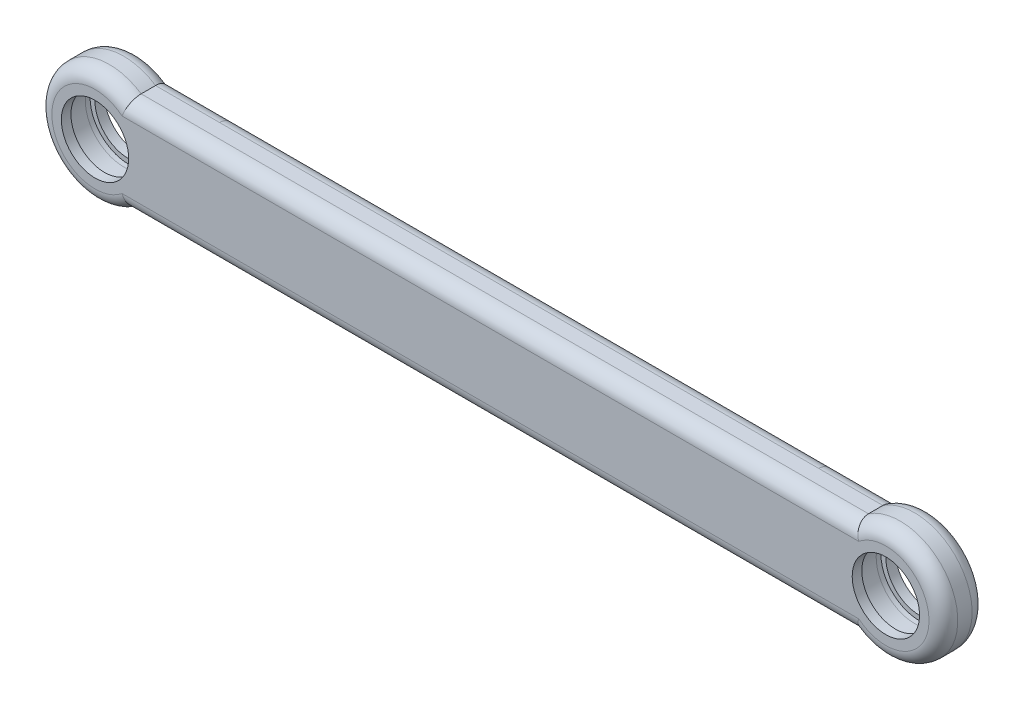
SolidWorks part; units mm, degrees
ref_plane "Front Plane" through (0, 0, 0) normal (0, 0, 1) x (1, 0, 0)
ref_plane "Top Plane" through (0, 0, 0) normal (0, 1, 0) x (1, 0, 0)
ref_plane "Right Plane" through (0, 0, 0) normal (1, 0, 0) x (0, 0, -1)
sketch "Sketch6" plane through (0, 0, 0) normal (0, 0, 1) x (1, 0, 0)
  line L0 (6.6332, -10) -> (158.3668, -10)
  line L2 (6.6332, 10) -> (158.3668, 10)
  line L3 (-58.5211, 0) -> (213.089, 0) construction
  line L6 (82.5, 22.0784) -> (82.5, -23.3181) construction
  line L13 (20, 10) -> (20, -10)
  line L14 (145, 10) -> (145, -10)
  circle A2 centre (165, 0) radius 12 construction
  circle A3 centre (0, 0) radius 8.025
  circle A4 centre (0, 0) radius 12 construction
  circle A8 centre (0, 0) radius 7.025
  circle A12 centre (13, 0) radius 2.2
  arc A14 (6.6332, 10) -> (6.6332, -10) centre (0, 0) ccw
  circle A15 centre (152, 0) radius 2.2
  circle A16 centre (165, 0) radius 7.025
  circle A17 centre (165, 0) radius 8.025
  arc A18 (158.3668, 10) -> (158.3668, -10) centre (165, 0) cw
  dimension "D2" = 1
  dimension "D3" = 165
  dimension "D4" = 16.05
  dimension "D5" = 24
  dimension "D6" = 1
  dimension "D7" = 7
  dimension "D8" = 20
  dimension "D10" = 4.4
extrude "Boss-Extrude1" add sketch "Sketch6" along normal blind 9 contours L2 A18 L0 A14
extrude "Cut-Extrude1" cut sketch "Sketch6<23>" along normal offset from surface (5 mm away) 2 from offset 2 contours A3 | A17 up to face at (82.5, 0, 9)
sketch "Sketch6<23>" plane through (0, 0, 0) normal (0, 0, 1) x (1, 0, 0) same geometry as "Sketch6"
extrude "Cut-Extrude2" cut sketch "Sketch6<24>" along normal through all contours A8 | A16
sketch "Sketch6<24>" plane through (0, 0, 0) normal (0, 0, 1) x (1, 0, 0) same geometry as "Sketch6"
fillet "Fillet1" radius 3 8 edges at (-12, 0, 9) (177, 0, 9) (82.5, -10, 9) (82.5, 10, 9) (82.5, -10, 0) (82.5, 10, 0) (177, 0, 0) (-12, 0, 0)
hole_wizard "CSK for M3 Flat Head Machine Screw1" positions "Sketch7" profile "Sketch8" countersink size "M3" standard "ANSI Metric"
sketch "Sketch7" plane through (0, 0, 0) normal (0, 0, -1) x (-1, 0, 0)
  line L1 (-82.5, 22.0784) -> (-82.5, -23.3181) construction
  point P0 (-152, 0)
  point P12 (-13, 0)
sketch "Sketch8" plane through (152, 0, 0) normal (1, 0, 0) x (0, 1, 0)
  line L0 (0, 0) -> (0, 4.0215)
  line L1 (0, 4.0215) -> (1.7, 3)
  line L2 (1.7, 3) -> (1.7, 1.45)
  line L3 (1.7, 1.45) -> (3.15, 0)
  line L5 (3.15, 0) -> (0, 0)
  line L6 (-1.7, 1.45) -> (-3.15, 0) construction
  line L10 (0, 4.0215) -> (-1.7, 3) construction
  line L11 (0, -6.35) -> (0, 107.95) construction
  dimension "Hole Dia." = 3.4
  dimension "Hole Depth" = 3
  dimension "Near C'Sink Dia." = 6.3
  dimension "Near C'Sink Angle" = 90
  dimension "Drill Angle" = 118
extrude "Cut-Extrude3" cut sketch "Sketch6<28>" along normal blind 5.5 from offset 3 contours A15 | A12
sketch "Sketch6<28>" plane through (0, 0, 0) normal (0, 0, 1) x (1, 0, 0) same geometry as "Sketch6"
sketch "Sketch9" plane through (0, 0, 0) normal (0, 1, 0) x (1, 0, 0)
  line L0 (-17.9046, -3) -> (20, -3)
  line L1 (20, -3) -> (20, 0)
  line L2 (-58.5211, 0) -> (213.089, 0) construction
  line L3 (82.5, 8.7338) -> (82.5, -17.0916) construction
  line L4 (145, -3) -> (145, 0)
  line L5 (182.9046, -3) -> (145, -3)
  dimension "D1" = 3
split "Split1" trim tools "Sketch9" bodies to split 136 resulting bodies 137 138 139
